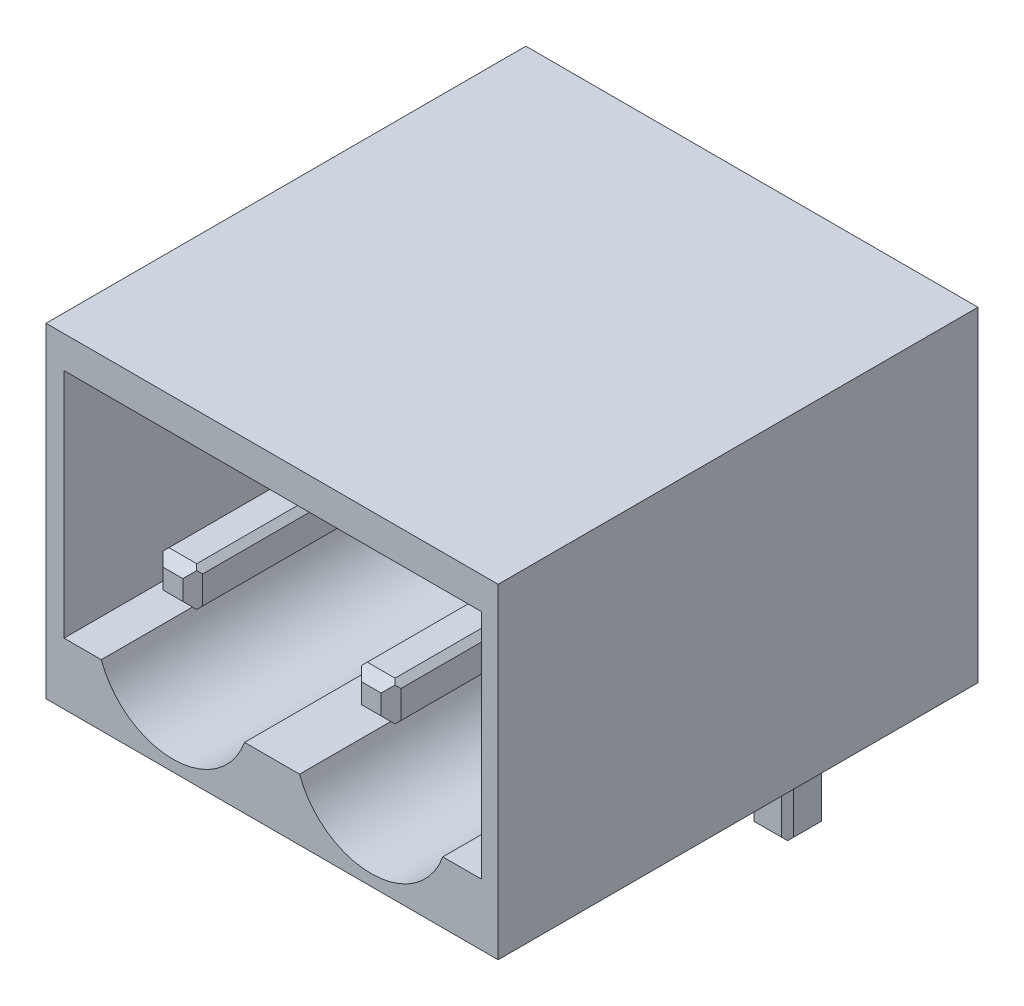
SolidWorks part; units mm, degrees
ref_plane "Спереди" through (0, 0, 0) normal (0, 0, 1) x (1, 0, 0)
ref_plane "Сверху" through (0, 0, 0) normal (0, 1, 0) x (1, 0, 0)
ref_plane "Справа" through (0, 0, 0) normal (1, 0, 0) x (0, 0, -1)
sketch "Эскиз1" plane through (0, 0, 0) normal (0, 0, 1) x (1, 0, 0)
  line L1 (-5.7, 4.1) -> (5.7, 4.1)
  line L2 (-5.7, 4.1) -> (-5.7, -4.1)
  line L3 (-5.7, -4.1) -> (5.7, -4.1)
  line L4 (5.7, 4.1) -> (5.7, -4.1)
  line L5 (-5.7, 4.1) -> (5.7, -4.1) construction
  line L6 (-5.7, -4.1) -> (5.7, 4.1) construction
  point P0 (0, 0)
  dimension "D1" = 8.2
  dimension "D2" = 11.4
extrude "Бобышка-Вытянуть1" add sketch "Эскиз1" along normal blind 12.1
sketch "Эскиз4" plane through (0, 0, 12.1) normal (0, 0, 1) x (1, 0, 0)
  circle A0 centre (-2.5, 0) radius 1.25
  circle A1 centre (2.5, 0) radius 1.25
  dimension "D1" = 2.5
  dimension "D2" = 2.5
  dimension "D3" = 2
extrude "Вырез-Вытянуть3" cut sketch "Эскиз4" against normal blind 8
sketch "Эскиз5" plane through (0, 0, 12.1) normal (0, 0, 1) x (1, 0, 0)
  line L0 (-5.2456, 0) -> (-5.2456, 3.2929)
  line L1 (-5.2456, 3.2929) -> (5.2785, 3.2929)
  line L2 (5.2785, 3.2929) -> (5.2785, -2.549)
  line L4 (-5.2456, -2.549) -> (-5.2456, 0)
  line L6 (-4.3058, -2.549) -> (-5.2456, -2.549)
  line L7 (-0.6942, -2.549) -> (0.6942, -2.549)
  line L8 (4.3058, -2.549) -> (5.2785, -2.549)
  arc A5 (-4.3058, -2.549) -> (-0.6942, -2.549) centre (-2.5, -1.9) ccw
  arc A6 (0.6942, -2.549) -> (4.3058, -2.549) centre (2.5, -1.9) ccw
  dimension "D1" = 3.2
  dimension "D2" = 2.2
  dimension "D3" = 2
extrude "Вырез-Вытянуть4" cut sketch "Эскиз5" against normal blind 7.8
sketch "Эскиз7" plane through (0, 0, 4.1) normal (0, 0, 1) x (1, 0, 0)
  line L0 (2, 0.5) -> (3, 0.5)
  line L1 (-3, 0.5) -> (-2, 0.5)
  line L2 (-3, 0.5) -> (-3, -0.5)
  line L3 (-3, -0.5) -> (-2, -0.5)
  line L4 (-2, 0.5) -> (-2, -0.5)
  line L5 (-3, 0.5) -> (-2, -0.5) construction
  line L6 (-3, -0.5) -> (-2, 0.5) construction
  line L7 (2, 0.5) -> (2, -0.5)
  line L8 (2, -0.5) -> (3, -0.5)
  line L9 (3, 0.5) -> (3, -0.5)
  line L10 (2, 0.5) -> (3, -0.5) construction
  line L11 (2, -0.5) -> (3, 0.5) construction
  point P0 (-2.5, 0)
  point P7 (2.5, 0)
  dimension "D1" = 1
  dimension "D2" = 1
  dimension "D3" = 2
extrude "Бобышка-Вытянуть2" add sketch "Эскиз7" along normal blind 8
chamfer "Фаска1" distance 0.15 angle 45 8 edges at (2, -0.5, 8.1) (2, 0.5, 8.1) (3, 0.5, 8.1) (3, -0.5, 8.1) (-2, -0.5, 8.1) (-2, 0.5, 8.1) (-3, -0.5, 8.1) (-3, 0.5, 8.1)
chamfer "Фаска2" distance 0.25 angle 45 8 edges at (2, 0, 12.1) (2.5, 0.5, 12.1) (3, 0, 12.1) (2.5, -0.5, 12.1) (-2, 0, 12.1) (-2.5, -0.5, 12.1) (-3, 0, 12.1) (-2.5, 0.5, 12.1)
sketch "Эскиз8" plane through (0, -4.1, 0) normal (0, -1, 0) x (-1, 0, 0)
  line L0 (-2, -2.1) -> (-3, -2.1)
  line L1 (3, -2.1) -> (2, -2.1)
  line L2 (3, -2.1) -> (3, -1.1)
  line L3 (3, -1.1) -> (2, -1.1)
  line L4 (2, -2.1) -> (2, -1.1)
  line L5 (3, -2.1) -> (2, -1.1) construction
  line L6 (3, -1.1) -> (2, -2.1) construction
  line L7 (-2, -2.1) -> (-2, -1.1)
  line L8 (-2, -1.1) -> (-3, -1.1)
  line L9 (-3, -2.1) -> (-3, -1.1)
  line L10 (-2, -2.1) -> (-3, -1.1) construction
  line L11 (-2, -1.1) -> (-3, -2.1) construction
  point P0 (2.5, -1.6)
  point P7 (-2.5, -1.6)
  dimension "D1" = 1
  dimension "D2" = 1
  dimension "D3" = 3.2
  dimension "D4" = 1.6
  dimension "D5" = 2
extrude "Бобышка-Вытянуть3" add sketch "Эскиз8" along normal blind 4
chamfer "Фаска3" distance 0.15 angle 45 8 edges at (-2, -6.1, 1.1) (3, -6.1, 1.1) (-3, -6.1, 1.1) (-2, -6.1, 2.1) (3, -6.1, 2.1) (2, -6.1, 1.1) (2, -6.1, 2.1) (-3, -6.1, 2.1)
chamfer "Фаска4" distance 0.25 angle 45 8 edges at (3, -8.1, 1.6) (2, -8.1, 1.6) (2.5, -8.1, 2.1) (2.5, -8.1, 1.1) (-3, -8.1, 1.6) (-2.5, -8.1, 2.1) (-2, -8.1, 1.6) (-2.5, -8.1, 1.1)
